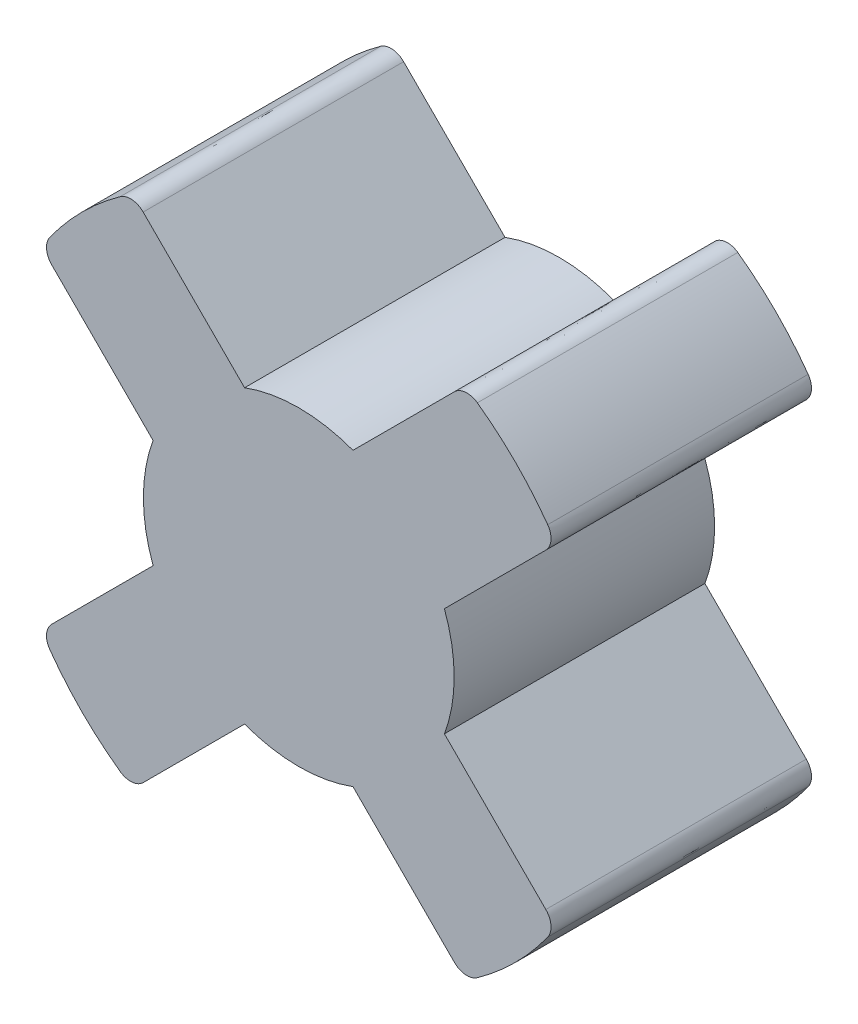
SolidWorks part; units mm, degrees
ref_plane "Alzado" through (0, 0, 0) normal (0, 0, 1) x (1, 0, 0)
ref_plane "Planta" through (0, 0, 0) normal (0, 1, 0) x (1, 0, 0)
ref_plane "Vista lateral" through (0, 0, 0) normal (1, 0, 0) x (0, 0, -1)
sketch "Sketch1" plane through (0, 0, 0) normal (0, 0, 1) x (1, 0, 0)
  line L0 (-9.3258, 14.4625) -> (-3.0436, 8.1803)
  line L1 (-11.8746, 6.7379) -> (-10.2188, 5.0821)
  line L2 (-5.0821, -10.2188) -> (-8.5196, -13.6563)
  line L3 (-10.2188, -5.0821) -> (-14.4625, -9.3258)
  line L8 (8.5196, -13.6563) -> (5.0821, -10.2188)
  line L9 (5.0821, 10.2188) -> (9.3258, 14.4625)
  line L10 (0, 0) -> (0, 15.0969) construction
  line L11 (9.3258, -14.4625) -> (3.0436, -8.1803)
  line L12 (-8.5196, 13.6563) -> (-9.3258, 14.4625)
  line L13 (-5.0821, 10.2188) -> (-3.2325, 8.3692)
  line L14 (-3.2325, 8.3692) -> (-3.0436, 8.1803)
  line L15 (-10.2188, 5.0821) -> (-8.1803, 3.0436)
  line L16 (5.0821, 10.2188) -> (9.3258, 14.4625)
  line L17 (8.5196, 13.6563) -> (5.0821, 10.2188)
  line L18 (5.0821, 10.2188) -> (3.0436, 8.1803)
  line L19 (8.1803, 3.0436) -> (14.4625, 9.3258)
  line L20 (13.6563, 8.5196) -> (10.2188, 5.0821)
  line L21 (10.2188, 5.0821) -> (8.1803, 3.0436)
  line L22 (8.1803, -3.0436) -> (14.4625, -9.3258)
  line L23 (13.6563, -8.5196) -> (10.2188, -5.0821)
  line L24 (10.2188, -5.0821) -> (8.1803, -3.0436)
  line L25 (3.2325, -8.3692) -> (9.3258, -14.4625)
  line L26 (8.5196, -13.6563) -> (5.0821, -10.2188)
  line L27 (5.0821, -10.2188) -> (3.2325, -8.3692)
  line L28 (-5.0821, -10.2188) -> (-9.3258, -14.4625)
  line L29 (-8.5196, -13.6563) -> (-5.0821, -10.2188)
  line L30 (-5.0821, -10.2188) -> (-3.0436, -8.1803)
  line L31 (-10.2188, -5.0821) -> (-14.4625, -9.3258)
  line L32 (-13.6563, -8.5196) -> (-10.2188, -5.0821)
  line L33 (-10.2188, -5.0821) -> (-8.1803, -3.0436)
  line L34 (-8.1803, 3.0436) -> (-14.4625, 9.3258)
  arc A1 (-9.776, 14.162) -> (-9.776, -14.162) centre (0, 0) ccw construction
  arc A4 (-2.0815, -8.4764) -> (2.0815, -8.4764) centre (0, 0) ccw
  arc A6 (9.7757, -14.1622) -> (9.776, 14.162) centre (0, 0) ccw construction
  arc A9 (2.0815, 8.4764) -> (-2.0815, 8.4764) centre (0, 0) ccw construction
  arc A11 (-14.4625, -9.3258) -> (-9.3258, -14.4625) centre (0, 0) ccw
  arc A12 (-8.1803, 3.0436) -> (-8.1803, -3.0436) centre (0, 0) ccw
  arc A13 (-9.3258, 14.4625) -> (-14.4625, 9.3258) centre (0, 0) ccw
  arc A14 (14.4625, 9.3258) -> (9.3258, 14.4625) centre (0, 0) ccw
  arc A15 (9.3258, -14.4625) -> (14.4625, -9.3258) centre (0, 0) ccw
  arc A16 (-3.0436, -8.1803) -> (3.0436, -8.1803) centre (0, 0) ccw
  arc A17 (8.1803, -3.0436) -> (8.1803, 3.0436) centre (0, 0) ccw
  arc A18 (3.0436, 8.1803) -> (-3.0436, 8.1803) centre (0, 0) ccw
  point P71 (0, 0)
  dimension "D1" = 4
extrude "Boss-Extrude1" add sketch "Sketch1" along normal blind 14.63 contours L18 A18 L0 A13 L34 L1 L15 A12 L33 L3 L31 A11 L28 L2 L30 A16 A4 L11 L8 A15 L22 A17 L19 A14 L16 L9 region at (0, 0, 0)
fillet "Fillet1" radius 1 8 edges at (14.4625, -9.3258, 7.315) (9.3258, -14.4625, 7.315) (-9.3258, -14.4625, 7.315) (-14.4625, -9.3258, 7.315) (-14.4625, 9.3258, 7.315) (-9.3258, 14.4625, 7.315) (9.3258, 14.4625, 7.315) (14.4625, 9.3258, 7.315) first distance on face at (12.0312, -12.0312, 7.315) first distance on face at (6.1847, -11.3214, 7.315) first distance on face at (-12.0312, -12.0312, 7.315) first distance on face at (-11.3214, -6.1847, 7.315) first distance on face at (-12.0312, 12.0312, 7.315) first distance on face at (-6.1847, 11.3214, 7.315) first distance on face at (12.0312, 12.0312, 7.315)
